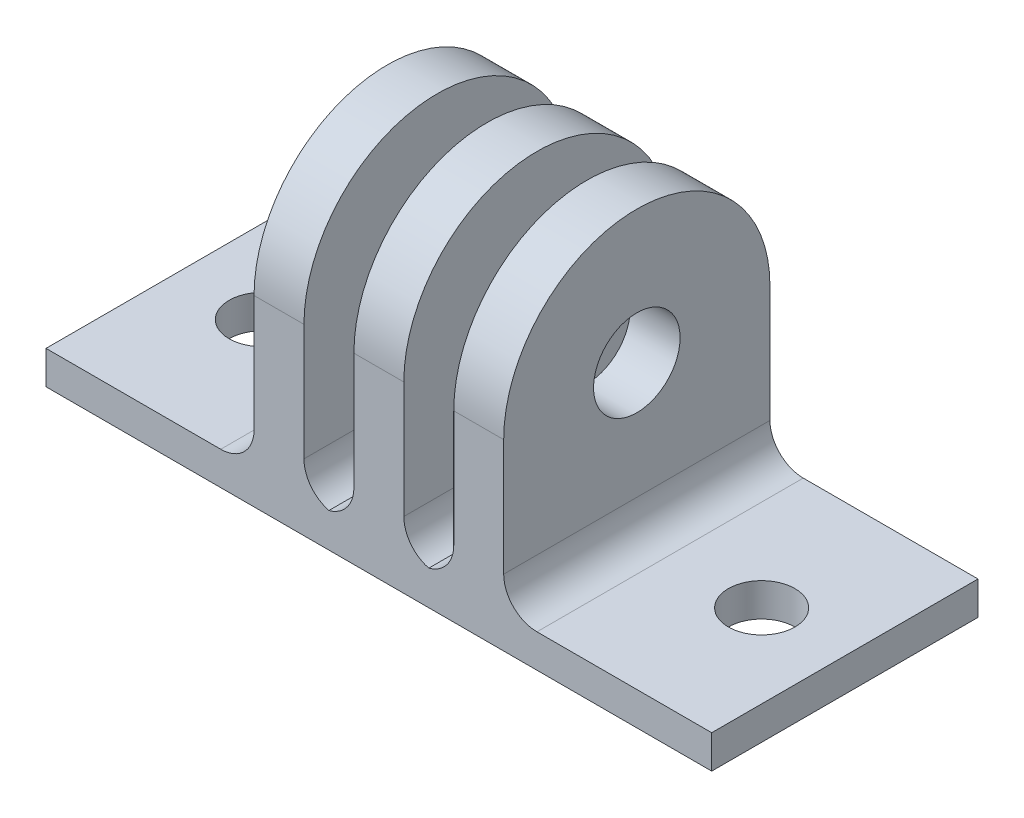
SolidWorks part; units mm, degrees
ref_plane "前基準面" through (0, 0, 0) normal (0, 0, 1) x (1, 0, 0)
ref_plane "上基準面" through (0, 0, 0) normal (0, 1, 0) x (1, 0, 0)
ref_plane "右基準面" through (0, 0, 0) normal (1, 0, 0) x (0, 0, -1)
sketch "草圖1" plane through (0, 0, 0) normal (0, 1, 0) x (1, 0, 0)
  line L1 (-20, -8) -> (20, -8)
  line L2 (-20, -8) -> (-20, 8)
  line L3 (-20, 8) -> (20, 8)
  line L4 (20, -8) -> (20, 8)
  line L5 (0, 8) -> (0, -8) construction
  line L6 (-20, 0) -> (20, 0) construction
  circle A0 centre (-15, 0) radius 2
  circle A1 centre (15, 0) radius 2
  point P0 (0, 0)
  dimension "D2" = 4
  dimension "D1" = 40
  dimension "D3" = 16
  dimension "D4" = 30
extrude "填料-伸長1" add sketch "草圖1" along normal blind 2
sketch "草圖2" plane through (0, 0, 0) normal (1, 0, 0) x (0, 0, -1)
  line L0 (-8, 2) -> (-8, 0) construction
  line L1 (8, 2) -> (-8, 2)
  line L2 (8, 2) -> (8, 11)
  line L3 (8, 11) -> (-8, 11) construction
  line L4 (-8, 2) -> (-8, 11)
  line L5 (0, -12.5876) -> (0, 12.5876) construction
  arc A0 (-8, 11) -> (8, 11) centre (0, 11) cw
  circle A1 centre (0, 11) radius 2.6
  point P10 (0, 2)
  point P12 (0, 0)
  dimension "D1" = 5.2
  dimension "D2" = 9
extrude "填料-伸長2" add sketch "草圖2" along normal mid plane 3 contours L5 L1 L2 L3 A1 | L5 A1 L3 A0 | L1 L5 A1 L3 L4 | A1 L5 A0 L3
pattern_linear "直線複製排列1" count 2 spacing 6 along (1, 0, 0) count 2 spacing 6 along (-1, 0, 0) of "填料-伸長2"
fillet "圓角1" radius 2 6 edges at (7.5, 2, 0) (-4.5, 2, 0) (-1.5, 2, 0) (-7.5, 2, 0) (4.5, 2, 0) (1.5, 2, 0)
